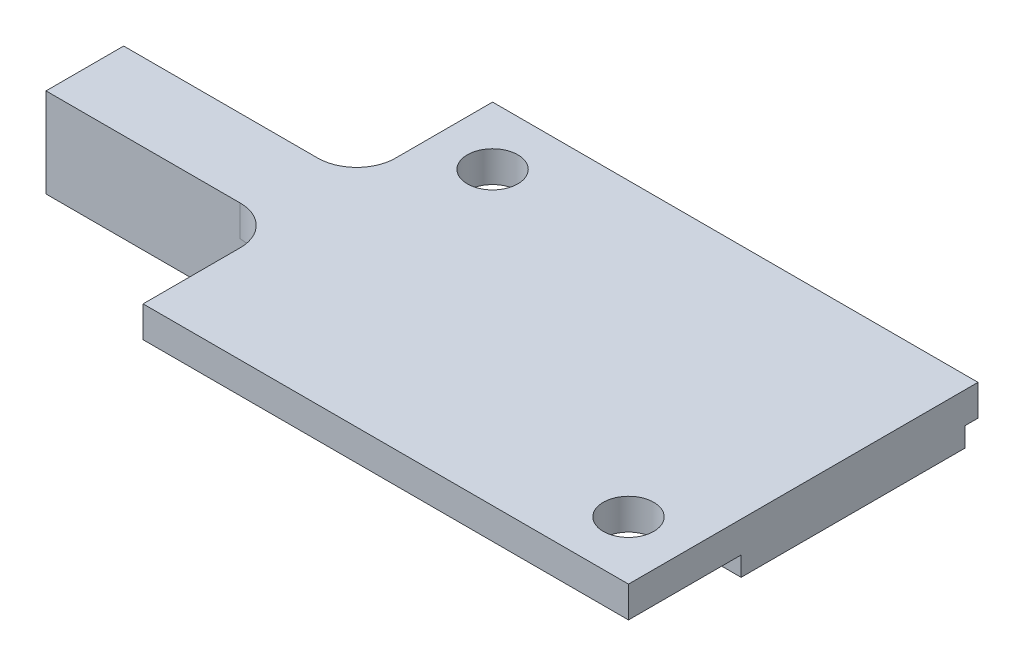
SolidWorks part; units mm, degrees
material "ABS"
ref_plane "Front Plane" through (0, 0, 0) normal (0, 0, 1) x (1, 0, 0)
ref_plane "Top Plane" through (0, 0, 0) normal (0, 1, 0) x (1, 0, 0)
ref_plane "Right Plane" through (0, 0, 0) normal (1, 0, 0) x (0, 0, -1)
sketch "Sketch1" plane through (0, 0, 0) normal (0, 1, 0) x (1, 0, 0)
  line L0 (0, 11) -> (0, 18)
  line L1 (0, 0) -> (25, 0)
  line L2 (0, 0) -> (0, 7)
  line L3 (0, 18) -> (25, 18)
  line L4 (25, 0) -> (25, 18)
  line L5 (0, 7) -> (-12, 7)
  line L7 (0, 11) -> (-12, 11)
  line L8 (-12, 7) -> (-12, 11)
  dimension "D1" = 18
  dimension "D2" = 25
  dimension "D3" = 4
  dimension "D4" = 12
  dimension "D5" = 7
extrude "Boss-Extrude1" add sketch "Sketch1" along normal blind 1.6
sketch "Sketch2" plane through (-12, 0, 0) normal (-1, 0, 0) x (0, 0, 1)
  line L0 (-9, 1.6) -> (-9, -4.9854) construction
  line L1 (-11, 1.6) -> (-7, 1.6) construction
  line L2 (-11, 0) -> (-7, 0) construction
  line L4 (-7, -3) -> (-7, 0)
  line L5 (-11, -3) -> (-11, 0)
  line L6 (-7, 0) -> (-11, 0)
  arc A0 (-7, -3) -> (-11, -3) centre (-9, -3) ccw
  line M1 (-11, 0) -> (-7, 0)
  dimension "D1" = 4
  dimension "D2" = 3
extrude "Boss-Extrude2" add sketch "Sketch2" against normal up to surface (12 mm away) contours A0 L4 L6 | A0 L5 M1 region at (-12, -0.7843, -9) up to face at (0, 0.8, -14.5)
sketch "Sketch3" plane through (0, 1.6, 0) normal (0, 1, 0) x (1, 0, 0)
  line L0 (0, 18) -> (0, 11) construction
  line L1 (25, 18) -> (0, 18) construction
  line L2 (25, 0) -> (25, 18) construction
  line L3 (0, 0) -> (25, 0) construction
  circle A0 centre (3, 15) radius 1.3
  circle A1 centre (22, 3) radius 1.3
  dimension "D1" = 2.6
  dimension "D2" = 2.6
  dimension "D3" = 3
  dimension "D4" = 3
  dimension "D5" = 3
  dimension "D6" = 3
extrude "Cut-Extrude1" cut sketch "Sketch3" against normal blind 1.6
fillet "Fillet1" radius 2 2 edges at (0, 0.8, -7) (0, 0.8, -11)
sketch "Sketch4" plane through (0, 0, 0) normal (0, -1, 0) x (1, 0, 0)
  line L0 (-12, -9) -> (28.8588, -9) construction
  line L1 (-12, -7) -> (-12, -11) construction
  line L2 (25, -5.8) -> (25, -17.33)
  line L3 (25, 0) -> (25, -18) construction
  line L4 (25, -17.33) -> (20.2856, -15.0198)
  line L5 (20.2856, -15.0198) -> (23, -11.947)
  line L6 (23, -11.947) -> (23, -5.8)
  line L7 (23, -5.8) -> (25, -5.8)
  line L8 (25, -18) -> (0, -18) construction
  dimension "D1" = 2
  dimension "D2" = 11.53
  dimension "D3" = 5.25
  dimension "D4" = 4.1
  dimension "D5" = 74.65
  dimension "D6" = 0.67
extrude "Boss-Extrude3" add sketch "Sketch4" along normal blind 1
equation "\"ˇ2\"=1.45231"
